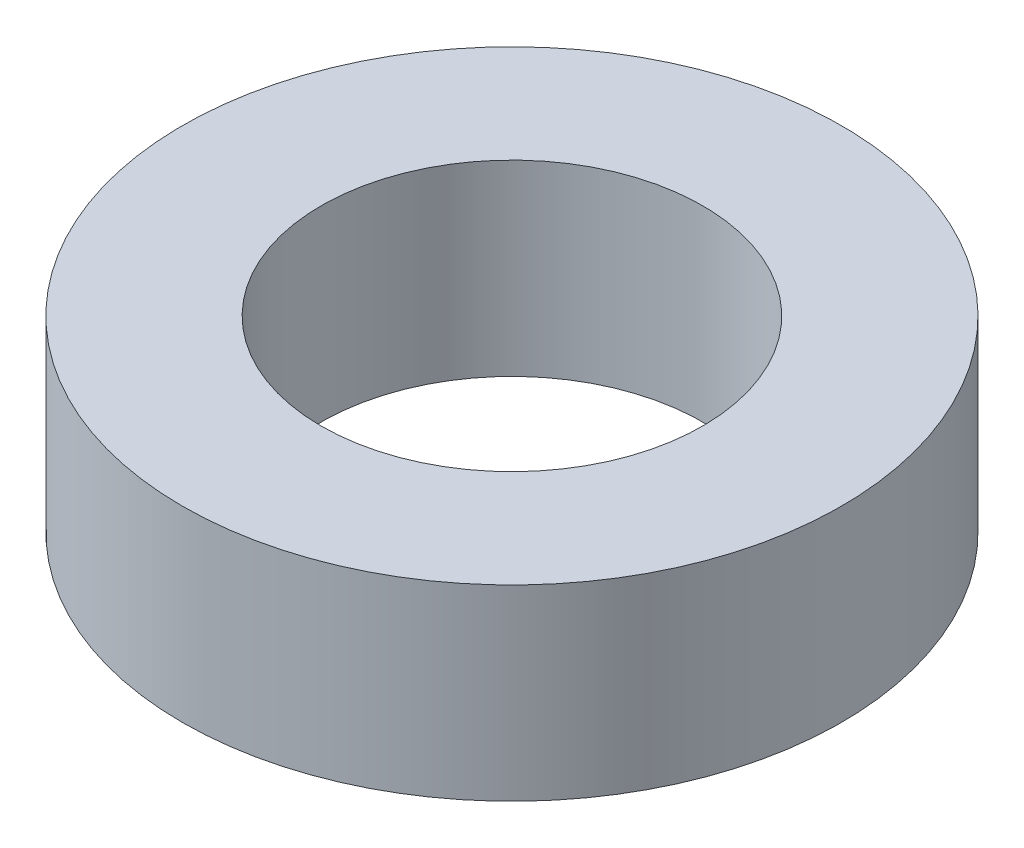
SolidWorks part; units mm, degrees
ref_plane "Front Plane" through (0, 0, 0) normal (0, 0, 1) x (1, 0, 0)
ref_plane "Top Plane" through (0, 0, 0) normal (0, 1, 0) x (1, 0, 0)
ref_plane "Right Plane" through (0, 0, 0) normal (1, 0, 0) x (0, 0, -1)
sketch "Sketch1" plane through (0, 0, 0) normal (0, 1, 0) x (1, 0, 0)
  circle A0 centre (0, 0) radius 47.5
  dimension "FLANGE_OD" = 95
extrude "Boss-Extrude1" add sketch "Sketch1" along normal blind 27
sketch "Sketch2" plane through (0, 0, 0) normal (0, 1, 0) x (1, 0, 0)
  circle A0 centre (0, 0) radius 27.5
  dimension "BORE_D" = 55
extrude "Cut-Extrude1" cut sketch "Sketch2" along normal through all
sketch "Sketch3" plane through (0, 27, 0) normal (0, 1, 0) x (1, 0, 0)
  circle A0 centre (0, 0) radius 17.0363 construction
  circle A1 centre (-17.0363, 0) radius 2.3667
  dimension "BOLT_D" = 4.7333
  dimension "BOLT_PCD" = 34.0726
extrude "Cut-Extrude2" cut sketch "Sketch3" against normal blind 22.8795 rebuild error yes
pattern_circular "CirPattern1" count 4 over 360 rebuild error yes
